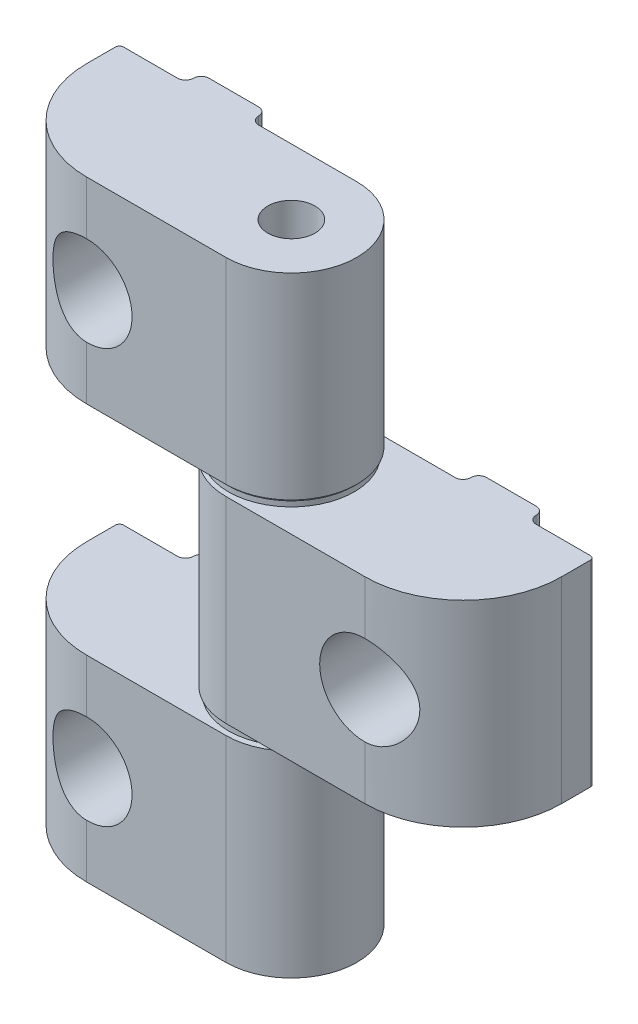
SolidWorks part; units mm, degrees
ref_plane "Front Plane" through (0, 0, 0) normal (0, 0, 1) x (1, 0, 0)
ref_plane "Top Plane" through (0, 0, 0) normal (0, 1, 0) x (1, 0, 0)
ref_plane "Right Plane" through (0, 0, 0) normal (1, 0, 0) x (0, 0, -1)
sketch "Sketch1" plane through (0, 0, 0) normal (0, 1, 0) x (1, 0, 0)
  line L0 (0, -6.35) -> (13.4874, -6.35)
  line L1 (22.6314, 6.35) -> (17.3736, 6.35)
  line L2 (23.0124, 5.969) -> (23.0124, 3.175)
  line L3 (11.049, 7.874) -> (15.8496, 7.874)
  line L6 (9.525, 6.35) -> (0, 6.35)
  circle A0 centre (0, 0) radius 6.35 construction
  arc A1 (13.4874, -6.35) -> (23.0124, 3.175) centre (13.4874, 3.175) ccw
  arc A2 (0, -6.35) -> (0, 6.35) centre (0, 0) cw
  circle A3 centre (0, 0) radius 2.286
  arc A4 (23.0124, 5.969) -> (22.6314, 6.35) centre (22.6314, 5.969) ccw
  arc A5 (9.525, 6.35) -> (10.287, 7.112) centre (9.525, 7.112) ccw
  arc A6 (10.287, 7.112) -> (11.049, 7.874) centre (11.049, 7.112) cw
  arc A7 (15.8496, 7.874) -> (16.6116, 7.112) centre (15.8496, 7.112) cw
  arc A8 (16.6116, 7.112) -> (17.3736, 6.35) centre (17.3736, 7.112) ccw
  point P11 (-6.35, 0)
  point P12 (-2.286, 0)
  point P19 (23.0124, 6.35)
  dimension "D1" = 12.7
  dimension "D4" = 4.572
  dimension "D8" = 0.381
  dimension "D7" = 0.762
  dimension "D2" = 29.3624
  dimension "D3" = 3.175
  dimension "D5" = 1.524
  dimension "D6" = 6.3246
  dimension "D9" = 6.4008
extrude "Boss-Extrude1" add sketch "Sketch1" along normal mid plane 19.05
sketch "Sketch2" plane through (0, 0, 0) normal (0, 0, 1) x (1, 0, 0)
  line L0 (0, 19.431) -> (0, -19.431)
  line L1 (0, 19.431) -> (-1.778, 19.431)
  line L2 (-1.778, 19.431) -> (-2.286, 19.431) construction
  line L3 (-2.286, 19.431) -> (-2.286, 18.923) construction
  line L4 (-2.286, 18.923) -> (-1.778, 19.431)
  line L5 (-2.286, 18.923) -> (-2.286, 10.287)
  line L6 (-2.286, 10.287) -> (-6.096, 10.287)
  line L7 (-6.096, 10.287) -> (-6.096, 9.779)
  line L8 (-6.096, 9.779) -> (-2.286, 9.779)
  line L9 (-2.286, 9.779) -> (-2.286, -9.779)
  line L10 (-2.286, -9.779) -> (-6.096, -9.779)
  line L11 (-6.096, -9.779) -> (-6.096, -10.287)
  line L12 (-6.096, -10.287) -> (-2.286, -10.287)
  line L13 (-2.286, -10.287) -> (-2.286, -18.923)
  line L14 (-2.286, -18.923) -> (-2.286, -19.431) construction
  line L15 (-2.286, -19.431) -> (-1.778, -19.431) construction
  line L16 (-1.778, -19.431) -> (0, -19.431)
  line L17 (-2.286, -18.923) -> (-1.778, -19.431)
  line L18 (-6.096, 9.779) -> (-6.096, -9.779) construction
  line L19 (-2.286, 10.287) -> (-2.286, 9.779) construction
  line L20 (-2.286, -10.287) -> (-2.286, -9.779) construction
  line L21 (0, 9.525) -> (-6.35, 9.525) construction
  dimension "D1" = 0.508
  dimension "D2" = 9.144
  dimension "D3" = 0.508
  dimension "D4" = 0.254
  dimension "D5" = 6.096
revolve "Revolve1" add sketch "Sketch2" angle 360 mid plane about L0
sketch "Sketch3" plane through (0, 0, 0) normal (0, 0, 1) x (1, 0, 0)
  line L0 (23.0124, 9.525) -> (23.0124, -9.525) construction
  line L1 (0, 0) -> (13.4366, 0) construction
  circle A0 centre (13.4366, 0) radius 2.4892
  dimension "D2" = 4.9784
  dimension "D1" = 9.5758
extrude "Cut-Extrude1" cut sketch "Sketch3" along normal through all and the other way through all
sketch "Sketch4" plane through (0, 0, -6.35) normal (0, 0, -1) x (-1, 0, 0)
  circle A0 centre (-13.4366, 0) radius 2.4892 construction
  circle A1 centre (-13.4366, 0) radius 2.4892
  circle A2 centre (-13.4366, 0) radius 4.2672
  dimension "D1" = 1.778
extrude "Boss-Extrude2" [suppressed] add sketch "Sketch4" along normal blind 2.159
sketch "Sketch5" plane through (0, 0, 6.35) normal (0, 0, 1) x (1, 0, 0)
  circle A0 centre (13.4366, 0) radius 4.3434
  dimension "D1" = 8.6868
extrude "Cut-Extrude2" cut sketch "Sketch5" against normal blind 7.1501
move or copy body "Body-Move/Copy1" bodies to move or copy 125 copy yes number of copies 1 translate (0, 20.066, 0)
move or copy body "Body-Move/Copy2" bodies to move or copy 125 copy yes number of copies 1 translate (0, -20.066, 0)
mirror "Mirror1" about plane through (0, 0, 0) normal (1, 0, 0) of bodies 126 127
delete or keep bodies "Body-Delete1" type delete bodies bodies 126 127
